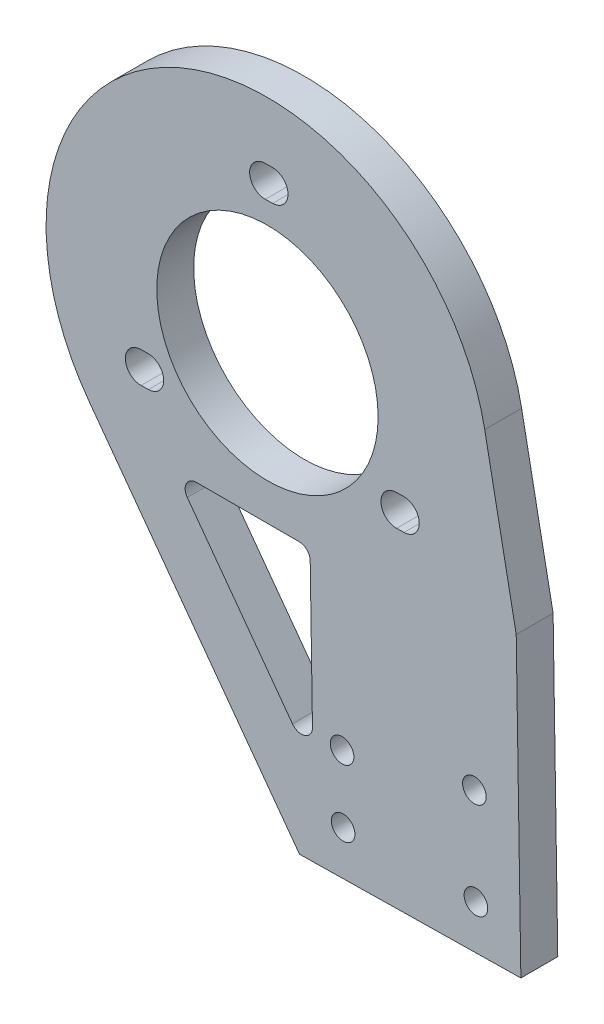
SolidWorks part; units mm, degrees
material "Thornel Mat VMA"
ref_plane "前视基准面" through (0, 0, 0) normal (0, 0, 1) x (1, 0, 0)
ref_plane "上视基准面" through (0, 0, 0) normal (0, 1, 0) x (1, 0, 0)
ref_plane "右视基准面" through (0, 0, 0) normal (1, 0, 0) x (0, 0, -1)
sketch "草图2" plane through (0, 0, 0) normal (0, 0, 1) x (1, 0, 0)
  line L9 (134.323, -112.3709) -> (130.0555, -90.4532)
  line L11 (76.4161, -113.9274) -> (104.9545, -152.8445)
  line L12 (104.9545, -152.8445) -> (134.9545, -152.3709)
  line L13 (134.2441, -107.3765) -> (135.2702, -172.3684) construction
  line L14 (134.9545, -152.3709) -> (134.323, -112.3709)
  line L15 (135.2702, -172.3684) -> (58.3983, -173.582) construction
  arc A0 (130.0555, -90.4532) -> (76.4161, -113.9274) centre (100.6084, -96.1868) ccw
  dimension "D1" = 60
  dimension "D2" = 40
  dimension "D3" = 20
  dimension "D4" = 30
extrude "凸台-拉伸1" add sketch "草图2" along normal blind 5
sketch "草图3" plane through (0, 0, 5) normal (0, 0, 1) x (1, 0, 0)
  line L0 (100.2927, -76.1899) -> (118.0841, -105.9118) construction
  line L1 (83.4485, -106.4587) -> (100.2927, -76.1899) construction
  line L2 (118.0841, -105.9118) -> (83.4485, -106.4587) construction
  circle A0 centre (100.6084, -96.1868) radius 15
  circle A1 centre (118.0841, -105.9118) radius 2.1
  circle A2 centre (83.4485, -106.4587) radius 2.1
  circle A3 centre (100.2927, -76.1899) radius 2.1
  circle A4 centre (100.6084, -96.1868) radius 19.9994 construction
  dimension "D1" = 30
  dimension "D2" = 4.2
  dimension "D6" = 34.64
extrude "切除-拉伸1" cut sketch "草图3" against normal blind 5
sketch "草图7" plane through (0, 0, 5) normal (0, 0, 1) x (1, 0, 0)
  line L0 (101.2926, -76.1741) -> (100.2927, -76.1899) construction
  line L1 (101.3258, -78.2738) -> (100.3259, -78.2896)
  line L2 (101.2595, -74.0743) -> (100.2596, -74.0901)
  line L3 (119.084, -105.896) -> (118.0841, -105.9118) construction
  line L4 (119.1172, -107.9958) -> (118.1173, -108.0116)
  line L5 (119.0509, -103.7963) -> (118.051, -103.8121)
  line L6 (84.4483, -106.4429) -> (83.4485, -106.4587) construction
  line L7 (84.4815, -108.5426) -> (83.4816, -108.5584)
  line L8 (84.4152, -104.3431) -> (83.4153, -104.3589)
  line L10 (104.9545, -152.8445) -> (134.9545, -152.3709) construction
  arc A0 (101.3258, -78.2738) -> (101.2595, -74.0743) centre (101.2926, -76.1741) ccw
  arc A1 (100.2596, -74.0901) -> (100.3259, -78.2896) centre (100.2927, -76.1899) ccw
  arc A2 (119.1172, -107.9958) -> (119.0509, -103.7963) centre (119.084, -105.896) ccw
  arc A3 (118.051, -103.8121) -> (118.1173, -108.0116) centre (118.0841, -105.9118) ccw
  arc A4 (84.4815, -108.5426) -> (84.4152, -104.3431) centre (84.4483, -106.4429) ccw
  arc A5 (83.4153, -104.3589) -> (83.4816, -108.5584) centre (83.4485, -106.4587) ccw
  circle A6 centre (100.2927, -76.1899) radius 2.1 construction
  circle A7 centre (118.0841, -105.9118) radius 2.1 construction
  circle A8 centre (83.4485, -106.4587) radius 2.1 construction
  point P3 (100.7927, -76.182)
  point P8 (118.5841, -105.9039)
  point P16 (83.9484, -106.4508)
  dimension "D1" = 1
  dimension "D2" = 1
  dimension "D3" = 1
extrude "切除-拉伸4" cut sketch "草图7" against normal blind 10
sketch "Sketch1" plane through (0, 0, 5) normal (0, 0, 1) x (1, 0, 0)
  circle A0 centre (110.7207, -137.7505) radius 1.6
  circle A1 centre (110.8628, -146.7505) radius 1.6
  circle A2 centre (128.8605, -146.4663) radius 1.6
  circle A3 centre (128.6553, -133.4663) radius 1.6
  dimension "D1" = 3.2
extrude "Cut-Extrude1" cut sketch "Sketch1" against normal blind 18
sketch "Sketch2" plane through (0, 0, 5) normal (0, 0, 1) x (1, 0, 0)
  line L0 (89.7438, -118.5738) -> (104.0006, -138.0153)
  line L2 (104.9032, -116.1868) -> (90.9535, -116.1868)
  line L3 (76.4161, -113.9274) -> (104.9545, -152.8445) construction
  line L6 (106.403, -117.6631) -> (106.71, -137.1046)
  circle A0 centre (100.6084, -96.1868) radius 15.8215 construction
  arc A1 (106.403, -117.6631) -> (104.9032, -116.1868) centre (104.9032, -117.6868) ccw
  arc A2 (89.7438, -118.5738) -> (90.9535, -116.1868) centre (90.9535, -117.6868) cw
  arc A3 (104.0006, -138.0153) -> (106.71, -137.1046) centre (105.2102, -137.1283) ccw
  dimension "D3" = 1.5
  dimension "D1" = 8
  dimension "D2" = 20
extrude "Cut-Extrude2" cut sketch "Sketch2" against normal blind 18
